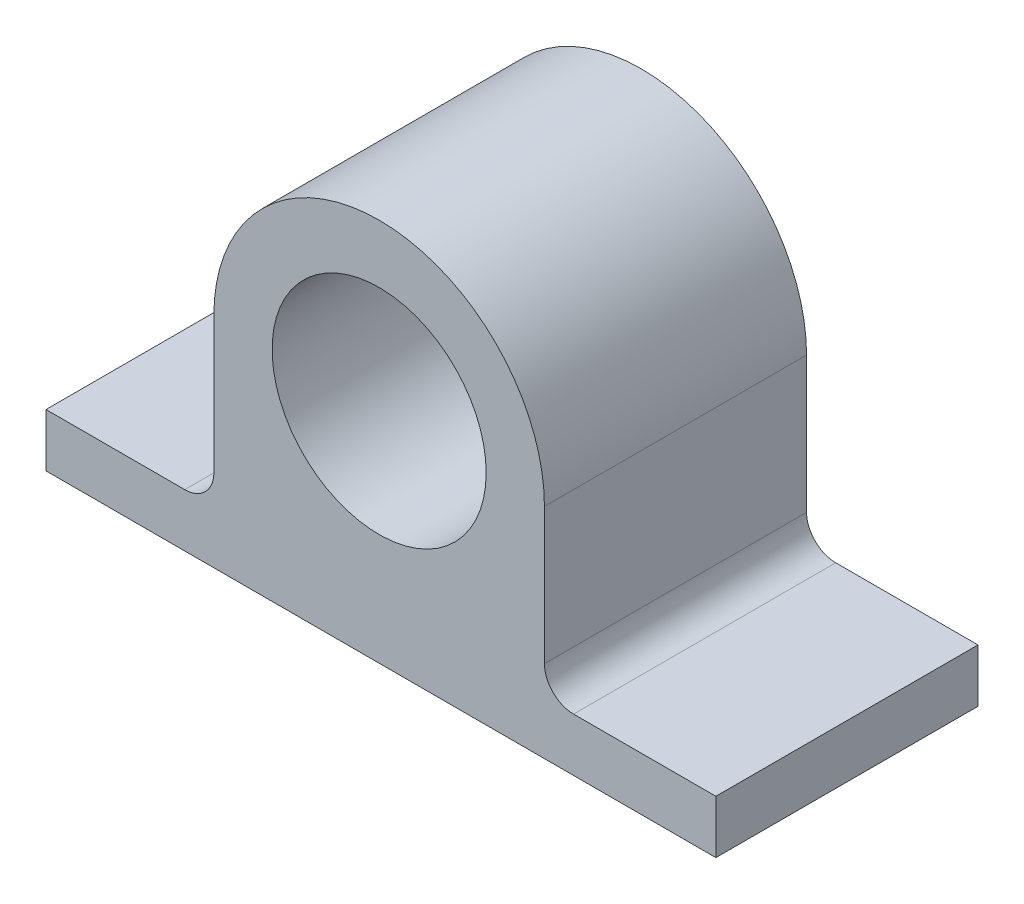
SolidWorks part; units mm, degrees
ref_plane "Front Plane" through (0, 0, 0) normal (0, 0, 1) x (1, 0, 0)
ref_plane "Top Plane" through (0, 0, 0) normal (0, 1, 0) x (1, 0, 0)
ref_plane "Right Plane" through (0, 0, 0) normal (1, 0, 0) x (0, 0, -1)
sketch "Sketch1" plane through (0, 0, 0) normal (0, 1, 0) x (1, 0, 0)
  line L1 (0, 0) -> (23, 0)
  line L2 (0, 0) -> (0, 9)
  line L3 (0, 9) -> (23, 9)
  line L4 (23, 0) -> (23, 9)
  dimension "D1" = 9
  dimension "D2" = 23
extrude "Boss-Extrude1" add sketch "Sketch1" along normal blind 15
sketch "Sketch2" plane through (0, 0, 0) normal (0, 0, 1) x (1, 0, 0)
  line L0 (5.7636, 15) -> (5.7636, 0)
  line L1 (0, 7.5) -> (23, 7.5) construction
  line L4 (0, 15) -> (0, 0) construction
  line L5 (23, 15) -> (23, 0) construction
  line L6 (0, 15) -> (23, 15) construction
  line L7 (0, 0) -> (23, 0) construction
  line L9 (23, 1.825) -> (0, 1.825)
  line L10 (17.1136, 15) -> (17.1136, 0)
  line L11 (0, 0) -> (23, 0) construction
  circle A0 centre (11.4386, 7.5) radius 3.675
  circle A1 centre (11.4386, 7.5) radius 3.625 construction
  circle A2 centre (11.4386, 7.5) radius 5.675
  line M6 (23, 0) -> (23, 15)
  line M7 (23, 15) -> (0, 15)
  line M8 (0, 15) -> (0, 0)
  dimension "D1" = 7.35
extrude "Cut-Extrude1" cut sketch "Sketch2" against normal through all contours L1 L0 M8 M7 | A2 L10 L0 M7 | L10 L1 M6 M7 | L1 A0 | A0 L1 | L1 L9 L0 M8 | L1 L10 L9 M6 region at (11.4386, 13.2149, 0) region at (2.8818, 11.25, 0) region at (2.8818, 4.6625, 0) region at (20.0568, 11.25, 0) region at (11.4386, 9.0597, 0) region at (11.4386, 5.9403, 0) region at (20.0568, 4.6625, 0)
fillet "Fillet1" radius 1 2 edges at (5.7636, 1.825, -4.5) (17.1136, 1.825, -4.5)
equation "\"circle diameter\"= 42mm"
equation "\"fillet rad\"= 2.5 * 2mm"
equation "\"carriage length\"= 100mm"
equation "\"carriage width\"= 15mm"
equation "\"carriage height\"= 30mm"
equation "\"rod diameter\"= 7.25mm"
equation "\"bracket width\"= 9mm"
equation "\"yoke width\"= 7mm"
equation "\"yoke height\"= 3mm"
equation "\"carriage lip width\"= 6mm"
equation "\"carriage lip height\"= 10mm"
equation "\"D1@Sketch1\"=\"bracket width\""
equation "\"D2@Sketch1\"=\"carriage lip width@scotch-yoke - assembly rods.SLDASM\"*2+\"carriage width@scotch-yoke - assembly rods.SLDASM\""
equation "\"D2@Sketch2\"=\"bracket thickness@scotch-yoke - assembly rods.SLDASM\""
equation "\"D1@Sketch2\"=\"rod diameter@scotch-yoke - assembly.Assembly\"+.1"
